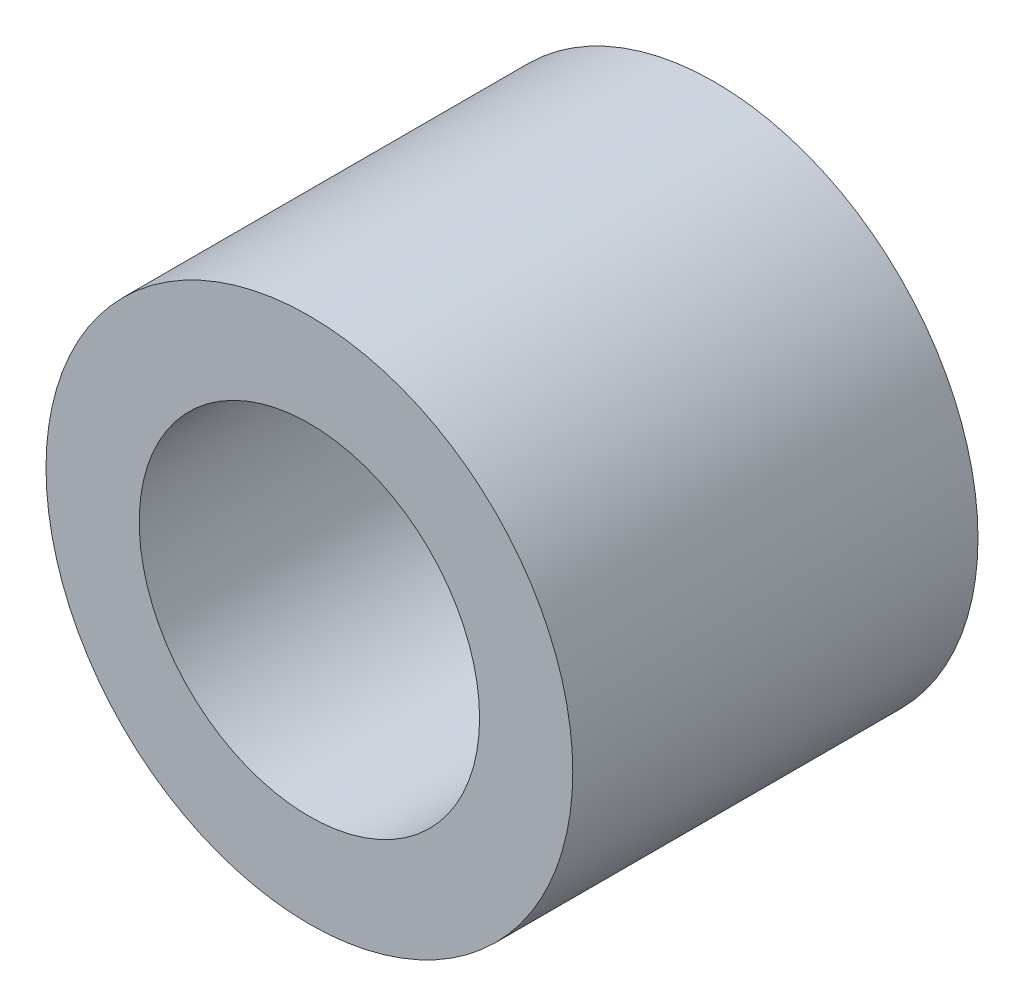
SolidWorks part; units mm, degrees
ref_plane "FRONT" through (0, 0, 0) normal (0, 0, 1) x (1, 0, 0)
ref_plane "TOP" through (0, 0, 0) normal (0, 1, 0) x (1, 0, 0)
ref_plane "RIGHT" through (0, 0, 0) normal (1, 0, 0) x (0, 0, -1)
ref_axis "X axis" through (88.99, 0, 0) along (-1, 0, 0)
ref_axis "Y axis" through (0, 55, 0) along (0, -1, 0)
ref_axis "Z axis" through (0, 0, 55) along (0, 0, -1)
sketch "Esquisse1" plane through (0, 0, 0) normal (0, 0, 1) x (1, 0, 0)
  circle A0 centre (0, 0) radius 3.25
  circle A1 centre (0, 0) radius 2.1
  dimension "D1" = 6.5
  dimension "D2" = 4.2
extrude "Boss.-Extru.1" add sketch "Esquisse1" against normal blind 1 contours A0
extrude "Boss.-Extru.2" add sketch "Esquisse1<3>" along normal blind 4
sketch "Esquisse1<3>" plane through (0, 0, 0) normal (0, 0, 1) x (1, 0, 0) same geometry as "Esquisse1"
